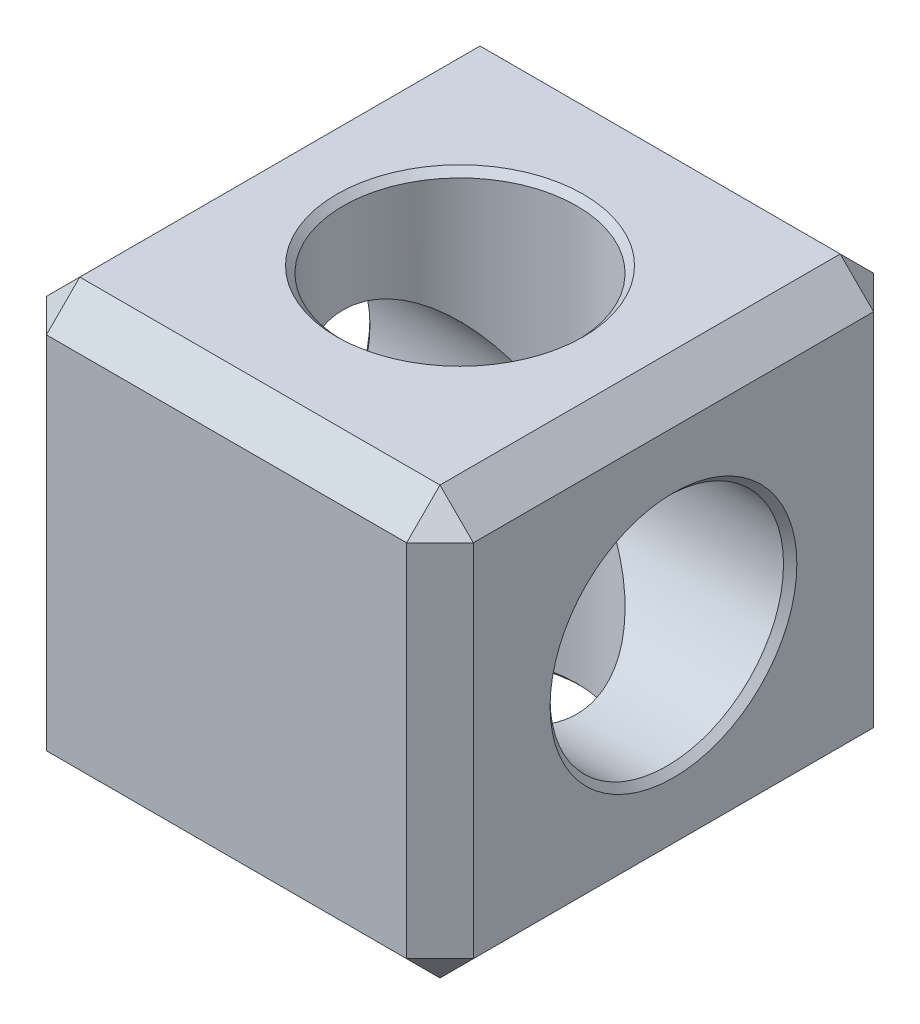
SolidWorks part; units mm, degrees
material "Malleable Cast Iron"
ref_plane "Front Plane" through (0, 0, 0) normal (0, 0, 1) x (1, 0, 0)
ref_plane "Top Plane" through (0, 0, 0) normal (0, 1, 0) x (1, 0, 0)
ref_plane "Right Plane" through (0, 0, 0) normal (1, 0, 0) x (0, 0, -1)
sketch "Sketch1" plane through (0, 0, 0) normal (0, 1, 0) x (1, 0, 0)
  line L1 (-32, -35) -> (32, -35)
  line L2 (-32, -35) -> (-32, 35)
  line L3 (-32, 35) -> (32, 35)
  line L4 (32, -35) -> (32, 35)
  line L5 (-32, -35) -> (32, 35) construction
  line L6 (-32, 35) -> (32, -35) construction
  point P0 (0, 0)
  dimension "D1" = 70
  dimension "D2" = 64
extrude "Boss-Extrude1" add sketch "Sketch1" along normal mid plane 64
sketch "Sketch2" plane through (0, 32, 0) normal (0, 1, 0) x (1, 0, 0)
  circle A0 centre (0, 0) radius 17.5
  dimension "D1" = 35
extrude "Cut-Extrude1" cut sketch "Sketch2" against normal through all
ref_axis "Axis2" through (0, 0, 38.5) along (0, 0, -1)
pattern_circular "CirPattern4" count 4 over 360 about axis through (0, 0, 38.5) along (0, 0, -1) of "Cut-Extrude1"
chamfer "Chamfer1" distance 5 angle 45 12 edges at (0, -32, 35) (32, 0, 35) (-32, 0, 35) (-32, -32, 0) (-32, 0, -35) (0, -32, -35) (0, 32, 35) (-32, 32, 0) (32, -32, 0) (32, 0, -35) (0, 32, -35) (32, 32, 0)
chamfer "Chamfer2" distance 1 angle 45 4 edges at (0, -32, 17.5) (32, 0, 17.5) (0, 32, 17.5) (-32, 0, 17.5)
